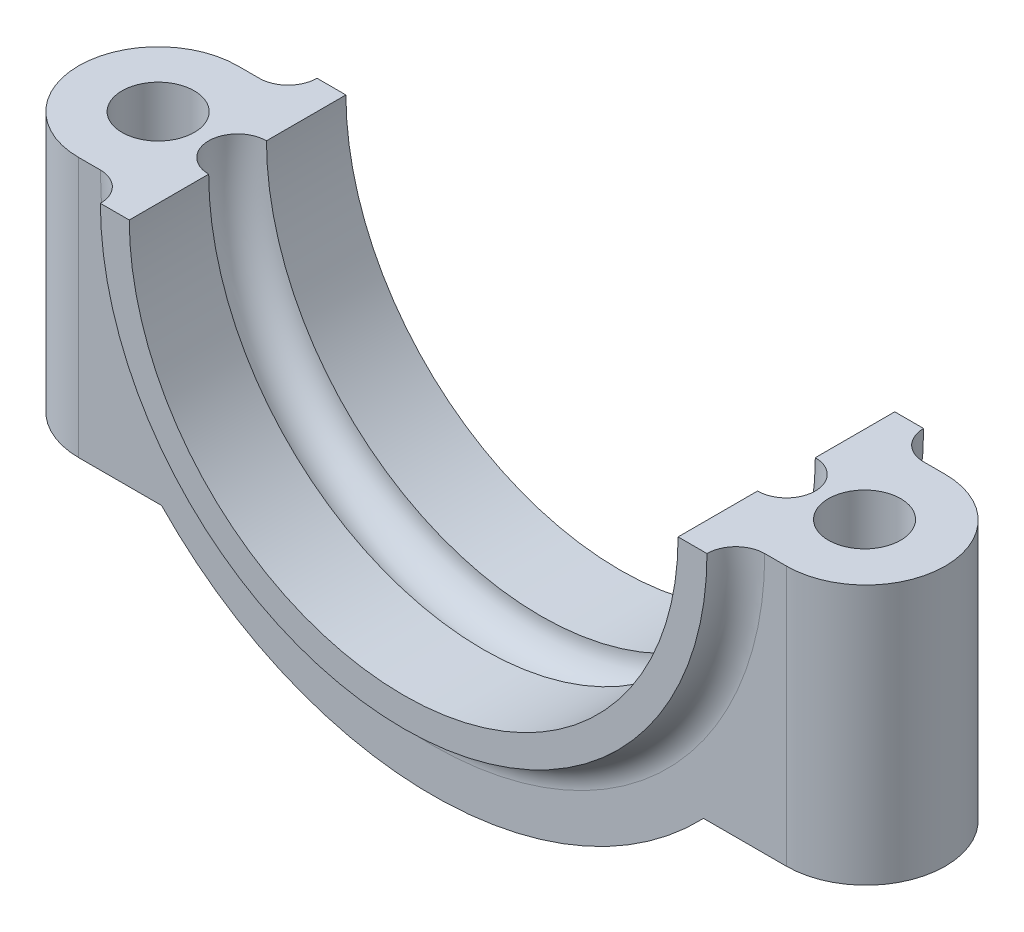
SolidWorks part; units mm, degrees
ref_plane "Front Plane" through (0, 0, 0) normal (0, 0, 1) x (1, 0, 0)
ref_plane "Top Plane" through (0, 0, 0) normal (0, 1, 0) x (1, 0, 0)
ref_plane "Right Plane" through (0, 0, 0) normal (1, 0, 0) x (0, 0, -1)
sketch "Sketch1" plane through (0, 0, 0) normal (0, 0, 1) x (1, 0, 0)
  line L0 (-30, 0) -> (30, 0) construction
  line L1 (0, 0) -> (0, -27.7578) construction
  line L2 (19, 0) -> (30, 0)
  line L3 (30, 0) -> (30, -18)
  line L4 (30, -18) -> (18.7617, -18)
  line L5 (-30, -18) -> (-18.7617, -18)
  line L6 (-30, 0) -> (-30, -18)
  line L7 (-19, 0) -> (-30, 0)
  arc A1 (-19, 0) -> (19, 0) centre (0, 0) ccw
  arc A2 (-18.7617, -18) -> (18.7617, -18) centre (0, 0) ccw
  point P4 (0, 0)
  dimension "D1" = 19
  dimension "D2" = 26
  dimension "D3" = 60
  dimension "D4" = 18
extrude "Boss-Extrude1" add sketch "Sketch1" along normal mid plane 11
sketch "Sketch2" plane through (0, 0, 0) normal (0, 0, 1) x (1, 0, 0)
  line L0 (-21, 0) -> (-19, 0)
  line L1 (19, 0) -> (21, 0)
  arc A0 (-19, 0) -> (19, 0) centre (0, 0) ccw construction
  arc A1 (-19, 0) -> (19, 0) centre (0, 0) ccw
  arc A2 (-21, 0) -> (21, 0) centre (0, 0) ccw
  dimension "D1" = 2
extrude "Boss-Extrude2" add sketch "Sketch2" along normal mid plane 15
sketch "Sketch3" plane through (0, 0, 0) normal (0, 1, 0) x (1, 0, 0)
  line L0 (-19, 0) -> (-30, 0) construction
  line L1 (19, 0) -> (30, 0) construction
  circle A0 centre (-24.5, 0) radius 2.5
  circle A1 centre (24.4095, 0) radius 2.5
  dimension "D1" = 5
  dimension "D2" = 5
extrude "Cut-Extrude1" cut sketch "Sketch3" against normal through all
fillet "Fillet1" radius 2 2 edges at (0, -21, -5.5) (0, -21, 5.5)
sketch "Sketch4" plane through (0, 0, 0) normal (0, 1, 0) x (1, 0, 0)
  line L1 (-19, -7.5) -> (-19, 7.5) construction
  line L2 (0, 0) -> (0, 6.8385) construction
  circle A1 centre (-19, 0) radius 2
revolve "Cut-Revolve1" cut sketch "Sketch4" angle 360 about L2
fillet "Fillet2" 2 edges at (-30, -9, -5.5) (-30, -9, 5.5) type full round first side face at (0, -12.875, -5.5) second side face at (0, -12.875, 5.5) middle face at (-30, -9, 0)
fillet "Fillet3" 2 edges at (30, -9, 5.5) (30, -9, -5.5) type full round first side face at (1.375, -12.875, 5.5) second side face at (1.375, -12.875, -5.5) middle face at (30, -9, 0)
